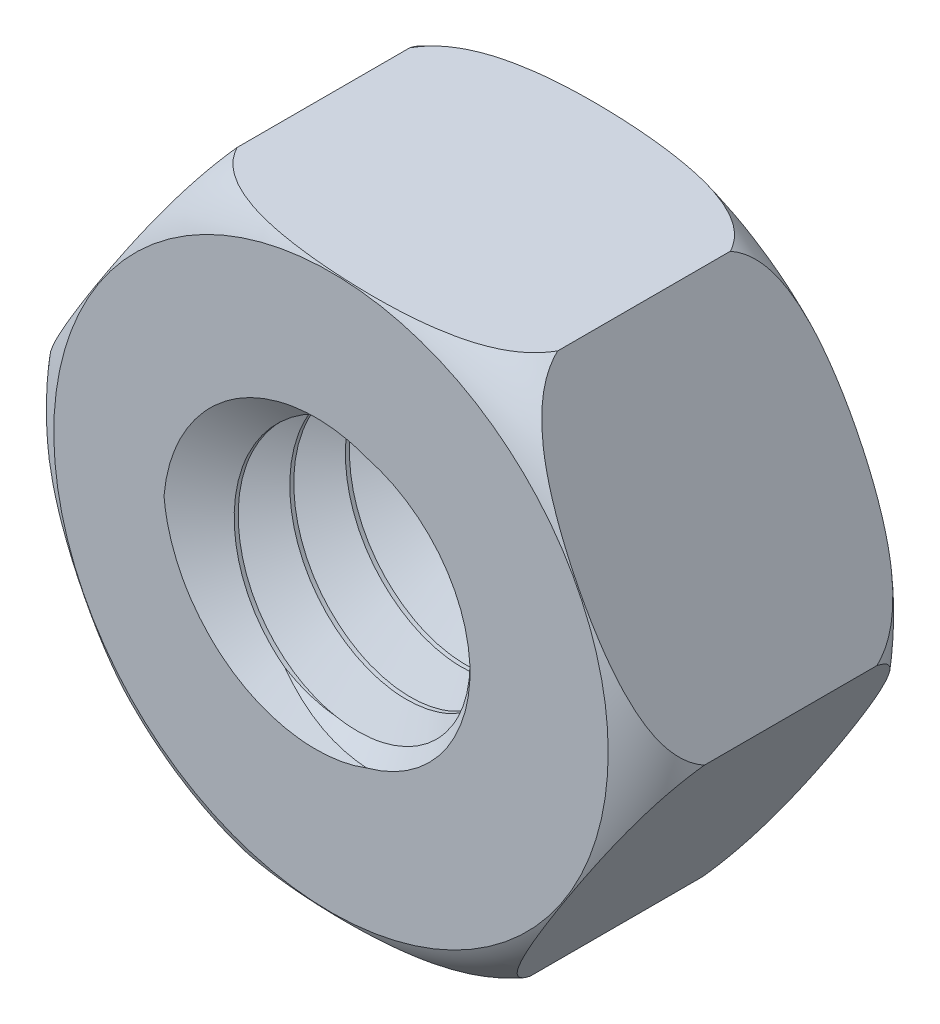
SolidWorks part; units mm, degrees
ref_plane "Ön Düzlem" through (0, 0, 0) normal (0, 0, 1) x (1, 0, 0)
ref_plane "Üst Düzlem" through (0, 0, 0) normal (0, 1, 0) x (1, 0, 0)
ref_plane "Sağ Düzlem" through (0, 0, 0) normal (1, 0, 0) x (0, 0, -1)
sketch "Sketch1" plane through (0, 0, 0) normal (0, 0, 1) x (1, 0, 0)
  line L7 (-3.1305, -4.8511) -> (2.636, -5.1366)
  line L8 (2.636, -5.1366) -> (5.7664, -0.2855)
  line L9 (5.7664, -0.2855) -> (3.1305, 4.8511)
  line L10 (3.1305, 4.8511) -> (-2.636, 5.1366)
  line L11 (-2.636, 5.1366) -> (-5.7664, 0.2855)
  line L12 (-5.7664, 0.2855) -> (-3.1305, -4.8511)
  circle A1 centre (0, 0) radius 5 construction
extrude "Boss-Extrude1" add sketch "Sketch1" along normal blind 5
ref_plane "Plane1" through (0, 0, 0) normal (0.8897, 0.4566, 0) x (0, 0, -1)
sketch "Sketch10" plane through (0, 0, 0) normal (0, 0, -1) x (-1, 0, 0)
  circle A0 centre (0, 0) radius 5
sketch "Sketch6" plane through (0, 0, 0) normal (0.8897, 0.4566, 0) x (0, 0, -1)
  line L1 (0, 5.7859) -> (-1, 5.7859)
  line L2 (0, 5.7859) -> (0, 4.9859)
  line L5 (0, 0) -> (1.7548, 0) construction
  spline S1 degree 2 poles (0, 4.9859) (-0.2974, 5.6287) (-1, 5.7859) knots 0 0 0 1 1 1
ref_plane "Plane2" through (0, 0, 2.5) normal (0, 0, -1) x (-1, 0, 0)
revolve "Cut-Revolve6" cut sketch "Sketch6" angle 360 about L5
mirror "Mirror1" about plane through (0, 0, 2.5) normal (0, 0, -1) of "Cut-Revolve6"
sketch "Sketch11" plane through (0, 0, 0) normal (0, 0, -1) x (-1, 0, 0)
  circle A0 centre (0, 0) radius 2.2
extrude "Cut-Extrude1" cut sketch "Sketch11" against normal blind 5
sketch "Sketch12" plane through (0, 0, 0) normal (0, 0, -1) x (-1, 0, 0)
  circle A0 centre (0, 0) radius 3
curve "Helix/Spiral2" pitch 1 height 6 radius 3 centre (0, 0, 0) axis (0, 0, 1) start towards (-1, 0, 0)
chamfer "Chamfer2" distance 0.3 angle 45 2 edges at (-2.2, 0, 5) (-2.2, 0, 0)
sketch "Sketch13" plane through (0, 0, 0) normal (0, 1, 0) x (1, 0, 0)
  line L0 (0, 0) -> (-3.0035, 0) construction
  line L1 (-2.1981, 0.465) -> (-2.1981, -0.465)
  line L5 (-3.0035, 0) -> (-2.1981, 0.465)
  line L6 (-2.1981, -0.465) -> (-3.0035, 0)
  dimension "D2" = 0.93
sweep "Cut-Sweep2" cut profiles "Sketch13" path "Helix/Spiral2"
